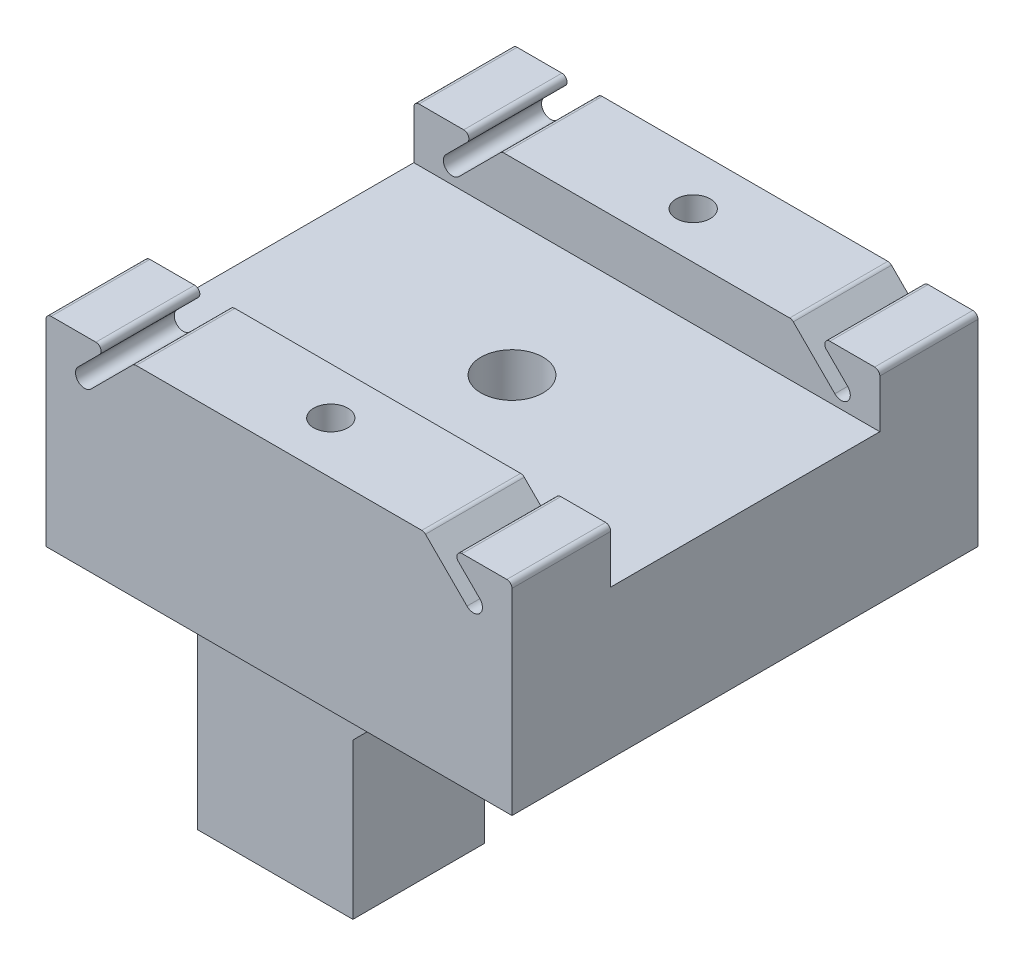
SolidWorks part; units mm, degrees
material "ABS"
ref_plane "Front Plane" through (0, 0, 0) normal (0, 0, 1) x (1, 0, 0)
ref_plane "Top Plane" through (0, 0, 0) normal (0, 1, 0) x (1, 0, 0)
ref_plane "Right Plane" through (0, 0, 0) normal (1, 0, 0) x (0, 0, -1)
sketch "Sketch1" plane through (0, 0, 0) normal (0, 0, 1) x (1, 0, 0)
  line L0 (22.5, 0) -> (-22.5, 0) construction
  line L6 (-22.5, 9.5) -> (22.5, 9.5)
  line L9 (-22.5, 9.5) -> (-22.5, -10)
  line L10 (-22.5, -10) -> (22.5, -10)
  line L11 (22.5, 9.5) -> (22.5, -10)
  point P8 (0, 0)
  dimension "D2" = 9.5
  dimension "D1" = 45
  dimension "D3" = 10
extrude "Boss-Extrude1" add sketch "Sketch1" along normal mid plane 45
sketch "Sketch3" plane through (0, 0, 0) normal (0, 0, 1) x (1, 0, 0)
  line L0 (0, 9.5) -> (0, -10)
  line L1 (0, -10) -> (8, -10)
  line L2 (8, -10) -> (8, -3.25)
  line L3 (8, -3.25) -> (6, -3.25)
  line L4 (6, -3.25) -> (6, 2.75)
  line L5 (6, 2.75) -> (8, 2.75)
  line L6 (8, 2.75) -> (8, 9.5)
  line L7 (8, 9.5) -> (0, 9.5)
  line L8 (22.5, 9.5) -> (-22.5, 9.5) construction
  line L9 (-22.5, -10) -> (22.5, -10) construction
  dimension "D1" = 6
  dimension "D2" = 8
  dimension "D3" = 6
revolve "Cut-Revolve1" [suppressed] cut sketch "Sketch3" angle 360 about L0
hole_wizard "M4x0.7 Tapped Hole2" positions "Sketch5" profile "Sketch4" tap size "M4x0.7" standard "ANSI Metric" end condition through all
sketch "Sketch5" plane through (0, -10, 0) normal (0, -1, 0) x (-1, 0, 0)
  line L0 (0, 17.5) -> (0, -17.5) construction
  line L2 (22.5, -22.5) -> (-22.5, -22.5) construction
  point P0 (0, -17.5)
  point P2 (0, 17.5)
  dimension "D1" = 5
sketch "Sketch4" plane through (0, -10, 17.5) normal (1, 0, 0) x (0, 0, -1)
  line L0 (0, 0) -> (0, 19.5)
  line L1 (0, 19.5) -> (1.65, 19.5)
  line L2 (1.65, 19.5) -> (1.65, 0)
  line L5 (1.65, 0) -> (0, 0)
  line L11 (0, -6.35) -> (0, 107.95) construction
  dimension "Thru Tap Drill Dia." = 3.3
  dimension "Thru Tap Drill Depth" = 19.5
cosmetic thread "Hole Thread1" parameters "D2"=4
cosmetic thread "Hole Thread2" parameters "D2"=4
sketch "Sketch7" plane through (0, 0, 0) normal (0, 0, 1) x (1, 0, 0)
  line L0 (-22.5, -7.5) -> (-24, -7.5)
  line L1 (-24, -7.5) -> (-24, -42.5)
  line L2 (-22.5, -10) -> (-22.5, -7.5)
  line L3 (-22.5, 9.5) -> (-22.5, -10) construction
  line L5 (8.5, -10) -> (-22.5, -10)
  line L7 (-24, -42.5) -> (-9, -42.5)
  line L8 (-9, -42.5) -> (-9, -27.5)
  line L9 (-9, -27.5) -> (8.5, -10)
  dimension "D1" = 24
  dimension "D2" = 35
  dimension "D3" = 15
  dimension "D4" = 45
  dimension "D5" = 2.5
  dimension "D6" = 15
extrude "Boss-Extrude3" add sketch "Sketch7" against normal mid plane 12.725
hole_wizard "M4x0.7 Tapped Hole1" positions "Sketch9" profile "Sketch8" tap size "M4x0.7" standard "ANSI Metric"
sketch "Sketch9" plane through (-24, 0, 0) normal (1, 0, 0) x (0, 0, -1)
  line L0 (6.3625, -42.5) -> (-6.3625, -42.5) construction
  point P0 (0, -37.5)
  point P2 (0, -22.5)
  dimension "D1" = 15
  dimension "D2" = 5
sketch "Sketch8" plane through (-24, -37.5, 0) normal (0, 1, 0) x (0, 0, 1)
  line L0 (0, 0) -> (0, 10.9914)
  line L1 (0, 10.9914) -> (1.65, 10)
  line L2 (1.65, 10) -> (1.65, 0)
  line L5 (1.65, 0) -> (0, 0)
  line L10 (0, 10.9914) -> (-1.65, 10) construction
  line L11 (0, -6.35) -> (0, 107.95) construction
  dimension "Tap Drill Dia." = 3.3
  dimension "Tap Drill Depth" = 10
  dimension "Drill Angle" = 118
cosmetic thread "Hole Thread5" parameters "D1"=8, "D2"=4
cosmetic thread "Hole Thread6" parameters "D1"=8, "D2"=4
sketch "Sketch10" plane through (0, 0, -6.3625) normal (0, 0, -1) x (-1, 0, 0)
  line L0 (22.5, -10) -> (24, -11.5)
  line L1 (24, -7.5) -> (24, -42.5) construction
  line L2 (24, -11.5) -> (24, -7.5)
  line L3 (24, -7.5) -> (22.5, -7.5)
  line L4 (22.5, -7.5) -> (22.5, -10)
  dimension "D1" = 45
extrude "Cut-Extrude2" cut sketch "Sketch10" against normal blind 85
sketch "Sketch2" plane through (0, 9.5, 0) normal (0, 1, 0) x (1, 0, 0)
  circle A0 centre (0, 0) radius 3
  dimension "D1" = 6
extrude "Cut-Extrude1" cut sketch "Sketch2" against normal blind 50
sketch "Sketch11" plane through (0, 0, 0) normal (0, 0, 1) x (1, 0, 0)
  line L0 (-16.4749, 9.5) -> (-20.0104, 5.9645)
  line L1 (22.5, 9.5) -> (-22.5, 9.5) construction
  line L2 (-20.0104, 5.9645) -> (-18.773, 4.727)
  line L3 (-18.773, 4.727) -> (-14, 9.5)
  line L4 (-14, 9.5) -> (-16.4749, 9.5)
  line L5 (0, 0) -> (0, 9.5) construction
  line L6 (14, 9.5) -> (16.4749, 9.5)
  line L7 (18.773, 4.727) -> (14, 9.5)
  line L8 (20.0104, 5.9645) -> (18.773, 4.727)
  line L9 (16.4749, 9.5) -> (20.0104, 5.9645)
  dimension "D1" = 45
  dimension "D2" = 1.75
  dimension "D3" = 6.75
  dimension "D4" = 14
extrude "Cut-Extrude3" cut sketch "Sketch11" against normal mid plane 50
fillet "Fillet1" 2 edges at (-20.0104, 5.9645, 0) (-18.773, 4.727, 0) type full round first side face at (-18.2426, 7.7322, 0) second side face at (-16.3865, 7.1135, 0) middle face at (-19.3917, 5.3457, 0)
fillet "Fillet2" 2 edges at (18.773, 4.727, 0) (20.0104, 5.9645, 0) type full round first side face at (16.3865, 7.1135, 0) second side face at (18.2426, 7.7322, 0) middle face at (19.3917, 5.3457, 0)
fillet "Fillet3" radius 0.5 6 edges at (-22.5, 9.5, 0) (-16.4749, 9.5, 0) (22.5, 9.5, 0) (16.4749, 9.5, 0) (-14, 9.5, 0) (14, 9.5, 0)
sketch "Sketch12" plane through (22.5, 0, 0) normal (1, 0, 0) x (0, 0, -1)
  line L1 (13.0203, 14.3786) -> (-12.9645, 14.3786)
  line L2 (13.0203, 14.3786) -> (13.0203, 4.3426)
  line L3 (13.0203, 4.3426) -> (-12.9645, 4.3426)
  line L4 (-12.9645, 14.3786) -> (-12.9645, 4.3426)
extrude "Cut-Extrude4" cut sketch "Sketch12" against normal blind 72.15
